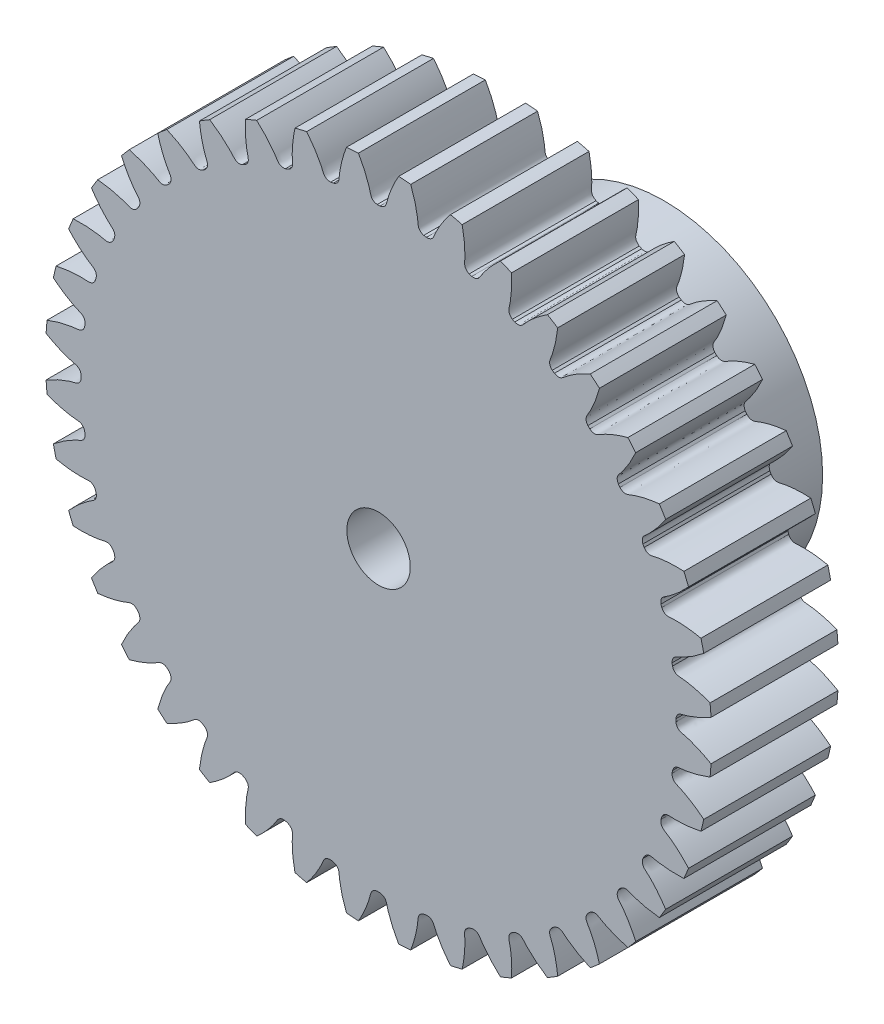
SolidWorks part; units mm, degrees
ref_plane "前视基准面" through (0, 0, 0) normal (0, 0, 1) x (1, 0, 0)
ref_plane "上视基准面" through (0, 0, 0) normal (0, 1, 0) x (1, 0, 0)
ref_plane "右视基准面" through (0, 0, 0) normal (1, 0, 0) x (0, 0, -1)
sketch "草图1" plane through (0, 0, 0) normal (0, 0, 1) x (1, 0, 0)
  circle A0 centre (0, 0) radius 10.5
extrude "凸台-拉伸1" add sketch "草图1" along normal blind 4
ref_axis "基准轴1" through (0, 0, -0.2) along (0, 0, 1)
sketch "草图2" plane through (0, 0, 0) normal (0, 0, 1) x (1, 0, 0)
  line L0 (0, 0) -> (0, 10.5) construction
  circle A0 centre (0, 0) radius 10.5 construction
  arc A1 (0.0423, 9.3749) -> (-0.0423, 9.3749) centre (0, 0) ccw
  arc A2 (1.8371, 11.939) -> (-1.8371, 11.939) centre (0, 0) ccw
  spline S0 degree 3 poles (0.0423, 9.3749) (0.2278, 9.402) (0.2447, 9.5352) (0.2835, 9.6781) (0.297, 9.7246) (0.3125, 9.7745) (0.3303, 9.8275) (0.3503, 9.8838) (0.3728, 9.9431) (0.3979, 10.0055) (0.4257, 10.0708) (0.4563, 10.139) (0.49, 10.21) (0.5267, 10.2836) (0.5666, 10.3598) (0.6098, 10.4385) (0.6565, 10.5196) (0.7067, 10.603) (0.7606, 10.6885) (0.8182, 10.776) (0.8797, 10.8655) (0.9452, 10.9568) (1.0148, 11.0498) (1.0885, 11.1443) (1.1664, 11.2402) (1.2487, 11.3375) (1.3354, 11.4359) (1.4266, 11.5353) (1.5223, 11.6356) (1.6579, 11.772) (1.7641, 11.8726) (1.8371, 11.939) knots 0 0 0 0 0.110657 0.124739 0.140005 0.156457 0.174093 0.192913 0.212918 0.234108 0.256483 0.280042 0.304786 0.330714 0.357827 0.386125 0.415607 0.446274 0.478126 0.511162 0.545383 0.580789 0.617379 0.655154 0.694113 0.734257 0.775586 0.8181 0.861798 0.906681 1 1 1 1
  spline S1 degree 3 poles (-0.0423, 9.3749) (-0.2278, 9.402) (-0.2447, 9.5352) (-0.2835, 9.6781) (-0.297, 9.7246) (-0.3125, 9.7745) (-0.3303, 9.8275) (-0.3503, 9.8838) (-0.3728, 9.9431) (-0.3979, 10.0055) (-0.4257, 10.0708) (-0.4563, 10.139) (-0.49, 10.21) (-0.5267, 10.2836) (-0.5666, 10.3598) (-0.6098, 10.4385) (-0.6565, 10.5196) (-0.7067, 10.603) (-0.7606, 10.6885) (-0.8182, 10.776) (-0.8797, 10.8655) (-0.9452, 10.9568) (-1.0148, 11.0498) (-1.0885, 11.1443) (-1.1664, 11.2402) (-1.2487, 11.3375) (-1.3354, 11.4359) (-1.4266, 11.5353) (-1.5223, 11.6356) (-1.6579, 11.772) (-1.7641, 11.8726) (-1.8371, 11.939) knots 0 0 0 0 0.110657 0.124739 0.140005 0.156457 0.174093 0.192913 0.212918 0.234108 0.256483 0.280042 0.304786 0.330714 0.357827 0.386125 0.415607 0.446274 0.478126 0.511162 0.545383 0.580789 0.617379 0.655154 0.694113 0.734257 0.775586 0.8181 0.861798 0.906681 1 1 1 1
extrude "切除-拉伸1" cut sketch "草图2" along normal through all
pattern_circular "阵列(圆周)1" count 40 every 9 about axis through (0, 0, -0.2) along (0, 0, 1) of "切除-拉伸1"
sketch "草图3" plane through (0, 0, 0) normal (0, 0, 1) x (1, 0, 0)
  circle A0 centre (0, 0) radius 10 construction
  dimension "Dn" = 20
sketch "草图4" plane through (0, 0, 0) normal (0, 0, -1) x (-1, 0, 0)
  circle A0 centre (0, 0) radius 5
  dimension "D1" = 10
extrude "凸台-拉伸2" add sketch "草图4" along normal blind 5
sketch "草图5" plane through (0, 0, -5) normal (0, 0, -1) x (-1, 0, 0)
  circle A0 centre (0, 0) radius 1
  dimension "D1" = 2
extrude "切除-拉伸2" cut sketch "草图5" against normal through all
sketch "草图6" plane through (0, 0, 0) normal (0, 1, 0) x (1, 0, 0)
  line L0 (0, 5) -> (0, 2.5) construction
  line L1 (1, 5) -> (-1, 5) construction
  circle A0 centre (0, 2.5) radius 1
  dimension "D2" = 2
  dimension "D1" = 2.5
extrude "切除-拉伸3" cut sketch "草图6" against normal through all both and the other way through all
fillet "圆角1" radius 1 1 edges at (5, 0, 0)
